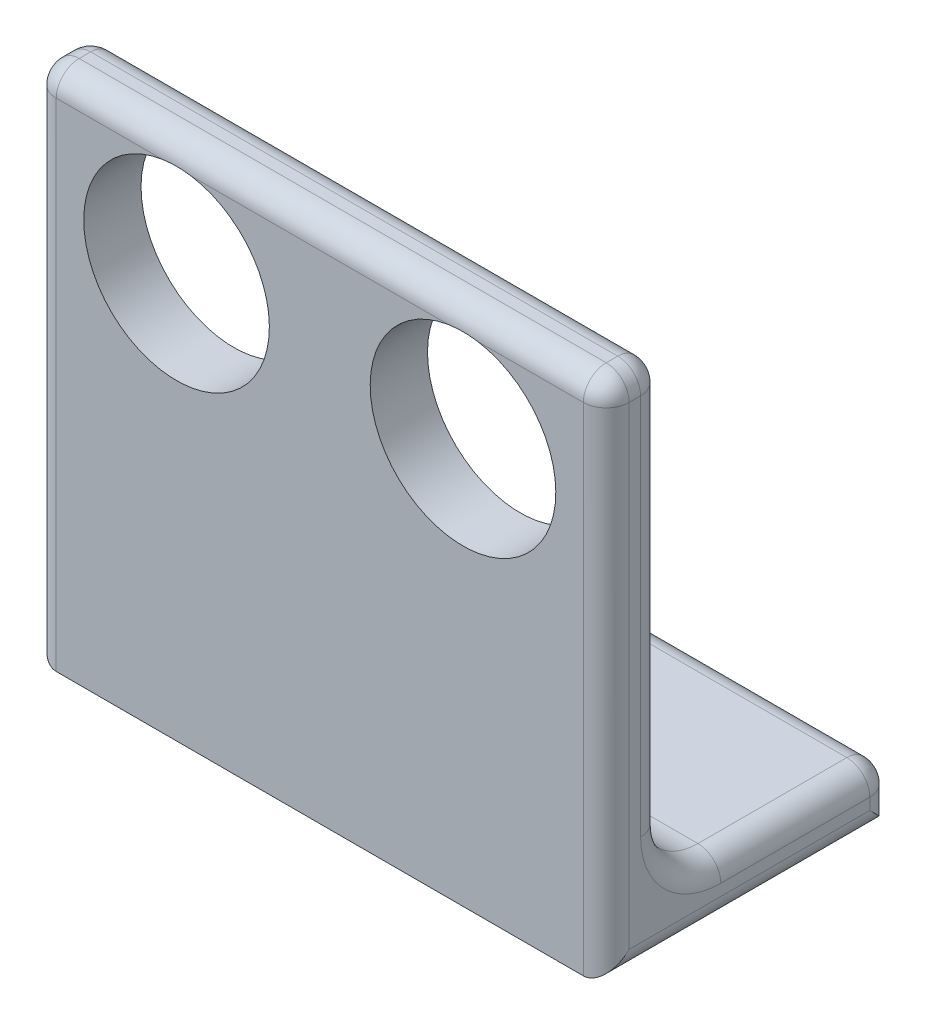
SolidWorks part; units mm, degrees
ref_plane "前视基准面" through (0, 0, 0) normal (0, 0, 1) x (1, 0, 0)
ref_plane "上视基准面" through (0, 0, 0) normal (0, 1, 0) x (1, 0, 0)
ref_plane "右视基准面" through (0, 0, 0) normal (1, 0, 0) x (0, 0, -1)
other "Configuration Table"
sketch "草图2" plane through (0, 0, 0) normal (0, 1, 0) x (1, 0, 0)
  line L1 (0, 0) -> (50, 0)
  line L2 (0, 0) -> (0, 25)
  line L3 (0, 25) -> (50, 25)
  line L4 (50, 0) -> (50, 25)
  dimension "D1" = 50
  dimension "D2" = 25
extrude "凸台-拉伸4" add sketch "草图2" along normal blind 5
sketch "草图7" plane through (0, 5, 0) normal (0, 1, 0) x (1, 0, 0)
  line L0 (50, 0) -> (50, 25) construction
  line L1 (0, 0) -> (50, 0)
  line L2 (0, 0) -> (0, 5)
  line L3 (0, 5) -> (50, 5)
  line L4 (50, 0) -> (50, 5)
  dimension "D1" = 5
extrude "凸台-拉伸5" add sketch "草图7" along normal blind 40.3395
sketch "草图8" plane through (0, 0, -5) normal (0, 0, -1) x (-1, 0, 0)
  line L0 (-50, 45.3395) -> (-50, 35.3395)
  line L1 (-50, 45.3395) -> (-50, 5) construction
  line L5 (-50, 45.3395) -> (0, 45.3395) construction
  line L8 (-37.5, 35.3395) -> (-37.5, 45.3395) construction
  circle A1 centre (-37.5, 35.3395) radius 8.1
  circle A2 centre (-12.5, 35.3395) radius 8.1
  point P5 (0, 0)
  point P22 (-19.4631, 34.3089)
  dimension "D1" = 10
fillet "圆角11" radius 2 1 edges at (25, 45.3395, 0)
fillet "圆角12" radius 2 1 edges at (25, 45.3395, -5)
fillet "圆角15" radius 5 1 edges at (25, 5, -5)
fillet "圆角17" radius 2 9 edges at (50, 6.4645, -6.4645) (50, 5, -17.5) (50, 2.5, -25) (50, 0, -12.5) (50, 21.6698, 0) (50, 44.7537, -0.5858) (50, 45.3395, -2.5) (50, 44.7537, -4.4142) (50, 26.6698, -5)
fillet "圆角18" radius 2 2 edges at (49.4142, 4.4142, -24.4142) (24, 5, -25)
fillet "圆角19" radius 2 10 edges at (0, 6.4645, -6.4645) (0, 26.6698, -5) (0, 44.7537, -4.4142) (0, 45.3395, -2.5) (0, 44.7537, -0.5858) (0, 21.6698, 0) (0, 0, -12.5) (0, 1.5, -25) (0, 4.4142, -24.4142) (0, 5, -16.5)
extrude "切除-拉伸4" cut sketch "草图8" against normal blind 25 contours A1 | A2
equation "\"25、2\"=11.1014"
